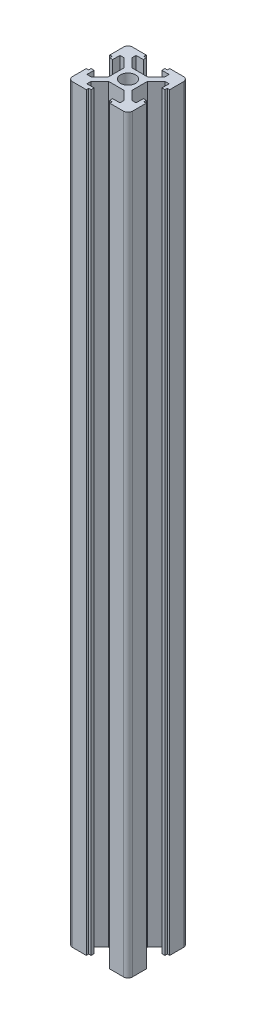
SolidWorks part; units mm, degrees
material "6063-O"
ref_plane "Front Plane" through (0, 0, 0) normal (0, 0, 1) x (1, 0, 0)
ref_plane "Top Plane" through (0, 0, 0) normal (0, 1, 0) x (1, 0, 0)
ref_plane "Right Plane" through (0, 0, 0) normal (1, 0, 0) x (0, 0, -1)
sketch "Sketch1" plane through (0, 0, 0) normal (0, 1, 0) x (1, 0, 0)
  line L0 (0, 14.5399) -> (0, 10) construction
  line L1 (-16.8658, 0) -> (2.5, 0) construction
  line L2 (13.2784, 3.9) -> (3.9, 3.9) construction
  line L3 (0, 0) -> (2.5, 0)
  line L4 (0, 0) -> (0, 2.5)
  line L5 (3.9, 10) -> (8.5, 10)
  line L6 (9.2, 0) -> (16.4291, 0) construction
  line L7 (-2.63, 3.9) -> (2.63, 3.9)
  line L9 (2.5491, 3.9) -> (2.63, 3.9)
  line L10 (3.9, 0) -> (3.9, 2.63)
  line L11 (13.2784, 3.1) -> (2.5491, 3.1) construction
  line L12 (8.2, 7.5573) -> (8.2, -3.0868) construction
  line L13 (9.2, 7.2593) -> (9.2, -8.1534) construction
  line L14 (10, 3.9) -> (9.2, 3.9)
  line L15 (9.2, 3.9) -> (9.2, 3.1)
  line L16 (9.2, 3.1) -> (8.2, 3.1)
  line L17 (8.2, 3.1) -> (8.2, 5.5)
  line L18 (8.2, 5.5) -> (6.77, 5.5)
  line L19 (6.77, 5.5) -> (3.9, 2.63)
  line L20 (5.0973, 5.5) -> (13.0082, 5.5) construction
  line L21 (3.1, 11.2046) -> (3.1, 2.6994) construction
  line L22 (3.9, 10.7498) -> (3.9, 3.9) construction
  line L23 (5.5, 11.523) -> (5.5, 1.4941) construction
  line L24 (-2.2597, 8.2) -> (6.1545, 8.2) construction
  line L25 (-2.9419, 9.2) -> (5.7225, 9.2) construction
  line L26 (3.9, 10) -> (3.9, 9.2)
  line L27 (3.9, 9.2) -> (3.1, 9.2)
  line L28 (3.1, 9.2) -> (3.1, 8.2)
  line L29 (3.1, 8.2) -> (5.5, 8.2)
  line L30 (5.5, 8.2) -> (5.5, 6.77)
  line L31 (5.5, 6.77) -> (2.63, 3.9)
  line L32 (0, 2.5) -> (0, -14.4122) construction
  line L33 (10, 3.9) -> (10, 8.5)
  line L34 (9.2, 0) -> (10, 0)
  line L35 (2.63, 3.9) -> (2.5491, 3.9) construction
  line L36 (3.9, 2.63) -> (3.9, 2.0627) construction
  line L37 (10, -3.9) -> (10, -8.5)
  line L38 (3.9, -10) -> (8.5, -10)
  line L39 (3.9, -10) -> (3.9, -9.2)
  line L40 (3.9, -9.2) -> (3.1, -9.2)
  line L41 (3.1, -9.2) -> (3.1, -8.2)
  line L42 (3.1, -8.2) -> (5.5, -8.2)
  line L43 (5.5, -8.2) -> (5.5, -6.77)
  line L44 (5.5, -6.77) -> (2.63, -3.9)
  line L45 (0, -3.9) -> (2.63, -3.9)
  line L46 (3.9, 0) -> (3.9, -2.63)
  line L47 (6.77, -5.5) -> (3.9, -2.63)
  line L48 (8.2, -5.5) -> (6.77, -5.5)
  line L49 (8.2, -3.1) -> (8.2, -5.5)
  line L50 (9.2, -3.1) -> (8.2, -3.1)
  line L51 (9.2, -3.9) -> (9.2, -3.1)
  line L52 (10, -3.9) -> (9.2, -3.9)
  line L53 (-3.9, -10) -> (-8.5, -10)
  line L54 (-10, -3.9) -> (-10, -8.5)
  line L55 (-10, -3.9) -> (-9.2, -3.9)
  line L56 (-9.2, -3.9) -> (-9.2, -3.1)
  line L57 (-9.2, -3.1) -> (-8.2, -3.1)
  line L58 (-8.2, -3.1) -> (-8.2, -5.5)
  line L59 (-8.2, -5.5) -> (-6.77, -5.5)
  line L60 (-6.77, -5.5) -> (-3.9, -2.63)
  line L61 (-3.9, 0) -> (-3.9, -2.63)
  line L62 (0, -3.9) -> (-2.63, -3.9)
  line L63 (-5.5, -6.77) -> (-2.63, -3.9)
  line L64 (-5.5, -8.2) -> (-5.5, -6.77)
  line L65 (-3.1, -8.2) -> (-5.5, -8.2)
  line L66 (-3.1, -9.2) -> (-3.1, -8.2)
  line L67 (-3.9, -9.2) -> (-3.1, -9.2)
  line L68 (-3.9, -10) -> (-3.9, -9.2)
  line L69 (-10, 3.9) -> (-10, 8.5)
  line L70 (-3.9, 10) -> (-8.5, 10)
  line L71 (-3.9, 10) -> (-3.9, 9.2)
  line L72 (-3.9, 9.2) -> (-3.1, 9.2)
  line L73 (-3.1, 9.2) -> (-3.1, 8.2)
  line L74 (-3.1, 8.2) -> (-5.5, 8.2)
  line L75 (-5.5, 8.2) -> (-5.5, 6.77)
  line L76 (-5.5, 6.77) -> (-2.63, 3.9)
  line L78 (-3.9, 0) -> (-3.9, 2.63)
  line L79 (-6.77, 5.5) -> (-3.9, 2.63)
  line L80 (-8.2, 5.5) -> (-6.77, 5.5)
  line L81 (-8.2, 3.1) -> (-8.2, 5.5)
  line L82 (-9.2, 3.1) -> (-8.2, 3.1)
  line L83 (-9.2, 3.9) -> (-9.2, 3.1)
  line L84 (-10, 3.9) -> (-9.2, 3.9)
  line L85 (0, 3.9) -> (-2.63, 3.9) [skipped]
  circle A0 centre (0, 0) radius 2.5
  arc A1 (8.5, 10) -> (10, 8.5) centre (8.5, 8.5) cw
  arc A2 (10, -8.5) -> (8.5, -10) centre (8.5, -8.5) cw
  arc A4 (-8.5, -10) -> (-10, -8.5) centre (-8.5, -8.5) cw
  arc A6 (-10, 8.5) -> (-8.5, 10) centre (-8.5, 8.5) cw
  point P12 (10, 10)
  point P126 (0, 0)
  dimension "D3" = 5
  dimension "D4" = 1.5
  dimension "D1" = 10
  dimension "D2" = 10
  dimension "D6" = 3.9
  dimension "D7" = 3.9
  dimension "D8" = 3.1
  dimension "D9" = 4
  dimension "D11" = 5.5
  dimension "D12" = 1.8
  dimension "D13" = 0.8
  dimension "D14" = 3.9
  dimension "D15" = 3.1
  dimension "D16" = 5.5
  dimension "D17" = 1.27
  dimension "D18" = 1.27
  dimension "D19" = 1.27
  dimension "D20" = 1.27
extrude "Boss-Extrude1" add sketch "Sketch1" along normal blind 250 contours A6 L69 L84 L83 L82 L81 L80 L79 L78 L61 L60 L59 L58 L57 L56 L55 L54 A4 L53 L68 L67 L66 L65 L64 L63 L62 L45 L44 L43 L42 L41 L40 L39 L38 A2 L37 L52 L51 L50 L49 L48 L47 L46 L10 L19 L18 L17 L16 L15 L14 L33 region at (6.2, 0, -9.7172)
